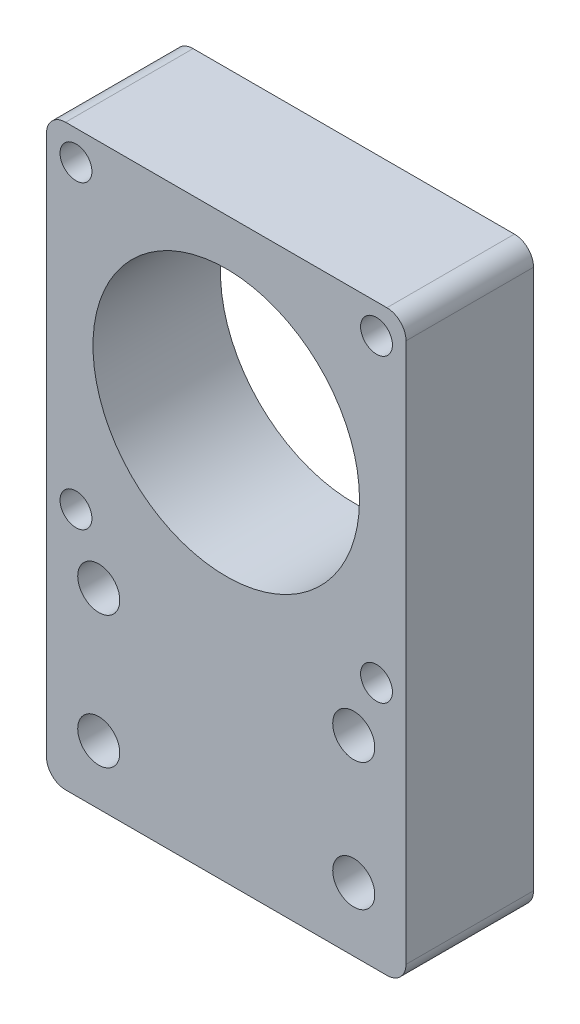
SolidWorks part; units mm, degrees
ref_plane "Front Plane" through (0, 0, 0) normal (0, 0, 1) x (1, 0, 0)
ref_plane "Top Plane" through (0, 0, 0) normal (0, 1, 0) x (1, 0, 0)
ref_plane "Right Plane" through (0, 0, 0) normal (1, 0, 0) x (0, 0, -1)
sketch "Sketch1" plane through (0, 0, 0) normal (0, 0, 1) x (1, 0, 0)
  line L4 (28.2, -3.2) -> (-28.2, -3.2)
  line L5 (28.2, 53.2) -> (28.2, -3.2)
  line L7 (-28.2, -3.2) -> (-28.2, 53.2)
  line L9 (-28.2, 53.2) -> (28.2, 53.2)
  point P4 (-28.2, 56.4053)
  point P8 (-28.8062, 58.9584)
  point P10 (-35.2523, 53.2)
  point P11 (37.2453, 53.2)
  point P12 (28.2, 57.4204)
  point P13 (-34.8379, -3.2)
  point P14 (35.1909, -3.2)
extrude "Boss-Extrude1" add sketch "Sketch1" along normal blind 20
sketch "Sketch2" plane through (0, 0, 20) normal (0, 0, 1) x (1, 0, 0)
  circle A3 centre (0, 25) radius 20.9044
  point P0 (-1.4169, 45.8563)
extrude "Cut-Extrude2" cut sketch "Sketch2" against normal blind 20
sketch "Sketch3" plane through (0, 0, 0) normal (0, 0, -1) x (-1, 0, 0)
  line L0 (28.2, -3.2) -> (-28.2, -3.2) construction
  line L1 (-28.2, -3.2) -> (28.2, -3.2)
  line L2 (-28.2, -3.2) -> (-28.2, -37.5)
  line L3 (-28.2, -37.5) -> (28.2, -37.5)
  line L4 (28.2, -3.2) -> (28.2, -37.5)
  line L5 (-28.2, -3.2) -> (-28.2, 53.2) construction
  line L7 (-126, -17.5) -> (126, -17.5) construction
  point P10 (28.2, -3.2)
  dimension "D1" = 20
extrude "Boss-Extrude2" add sketch "Sketch3" against normal blind 20
fillet "Fillet1" radius 3 4 edges at (28.2, -37.5, 10) (-28.2, -37.5, 10) (28.2, 53.2, 10) (-28.2, 53.2, 10)
hole_wizard "Tap Drill for M6 Tap1" positions "Sketch4" profile "Sketch5" hole size "M6" standard "ISO" end condition through all
sketch "Sketch4" plane through (0, 0, 0) normal (0, 0, -1) x (-1, 0, 0)
  point P0 (-23.57, 48.57)
  point P2 (23.57, 48.57)
  point P4 (-23.57, 1.43)
  point P6 (23.57, 1.43)
sketch "Sketch5" plane through (23.57, 48.57, 0) normal (1, 0, 0) x (0, 1, 0)
  line L0 (0, 0) -> (0, 20)
  line L1 (0, 20) -> (2.5, 20)
  line L2 (2.5, 20) -> (2.5, 0)
  line L5 (2.5, 0) -> (0, 0)
  line L11 (0, -6.35) -> (0, 107.95) construction
  dimension "Thru Hole Dia." = 5
  dimension "Thru Hole Depth" = 20
hole_wizard "M6 Clearance Hole1" positions "Sketch6" profile "Sketch7" hole size "M6" standard "ISO" end condition through all
sketch "Sketch6" plane through (0, 0, 0) normal (0, 0, -1) x (-1, 0, 0)
  point P0 (-20, -7.5)
  point P2 (-20, -27.5)
  point P4 (20, -28.2377)
  point P6 (20, -7.5)
sketch "Sketch7" plane through (20, -7.5, 0) normal (1, 0, 0) x (0, 1, 0)
  line L0 (0, 0) -> (0, 20)
  line L1 (0, 20) -> (3.3, 20)
  line L2 (3.3, 20) -> (3.3, 0)
  line L5 (3.3, 0) -> (0, 0)
  line L11 (0, -6.35) -> (0, 107.95) construction
  dimension "Thru Hole Dia." = 6.6
  dimension "Thru Hole Depth" = 20
